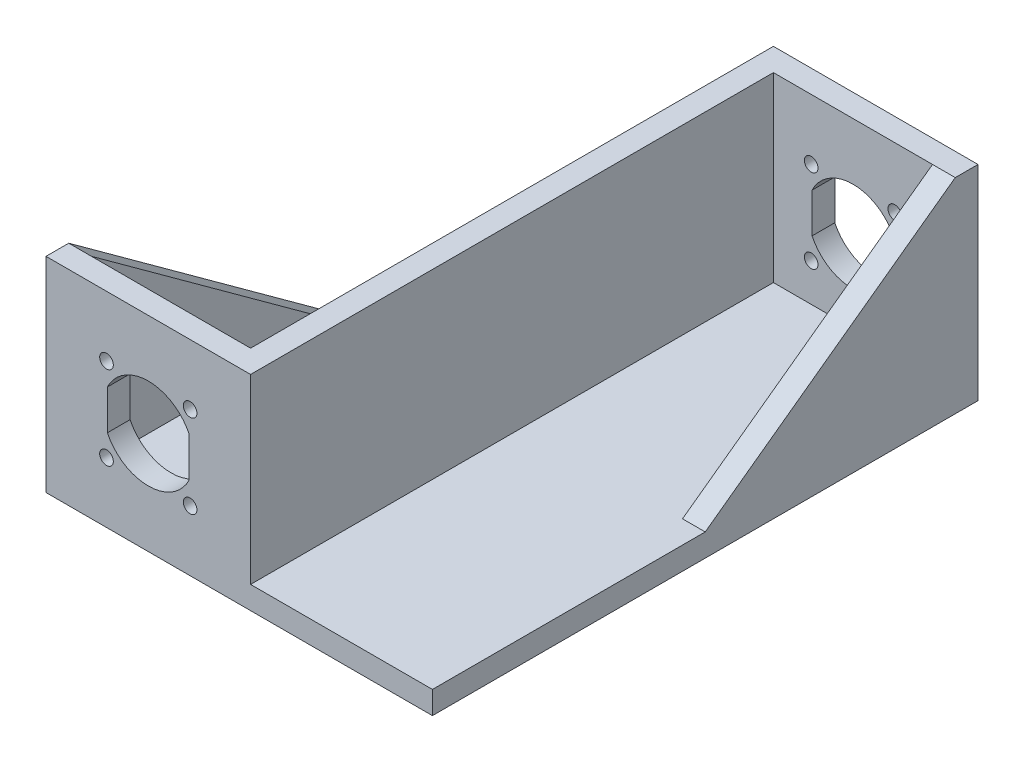
SolidWorks part; units mm, degrees
ref_plane "Plan de face" through (0, 0, 0) normal (0, 0, 1) x (1, 0, 0)
ref_plane "Plan de dessus" through (0, 0, 0) normal (0, 1, 0) x (1, 0, 0)
ref_plane "Plan de droite" through (0, 0, 0) normal (1, 0, 0) x (0, 0, -1)
sketch "Esquisse1" plane through (0, 0, 0) normal (0, 0, 1) x (1, 0, 0)
  line L0 (45, 0) -> (0, 45) construction
  line L1 (0, 0) -> (45, 0)
  line L2 (0, 0) -> (0, 45)
  line L3 (0, 45) -> (45, 45)
  line L4 (45, 0) -> (45, 45)
  line L5 (0, 0) -> (45, 45) construction
  line L6 (22.5, 45) -> (22.5, 0) construction
  line L7 (13.5, 26.8589) -> (13.5, 18.1411)
  line L8 (45, 22.5) -> (0, 22.5) construction
  line L9 (31.5, 26.8589) -> (31.5, 18.1411)
  arc A0 (13.5, 18.1411) -> (31.5, 18.1411) centre (22.5, 22.5) ccw
  circle A1 centre (31.6924, 31.6924) radius 1.5
  circle A2 centre (31.6924, 13.3076) radius 1.5
  circle A3 centre (13.3076, 13.3076) radius 1.5
  circle A4 centre (13.3076, 31.6924) radius 1.5
  arc A5 (31.5, 26.8589) -> (13.5, 26.8589) centre (22.5, 22.5) ccw
  dimension "D3" = 20
  dimension "D5" = 3
  dimension "D1" = 45
  dimension "D2" = 45
  dimension "D4" = 13
  dimension "D6" = 9
extrude "Extrusion1" add sketch "Esquisse1" along normal blind 5
sketch "Esquisse2" plane through (0, 0, 5) normal (0, 0, 1) x (1, 0, 0)
  line L0 (45, 0) -> (45, 45) construction
  line L1 (0, 0) -> (45, 0)
  line L2 (0, 0) -> (0, 5)
  line L3 (0, 5) -> (45, 5)
  line L4 (45, 0) -> (45, 5)
  dimension "D1" = 5
extrude "Extrusion2" add sketch "Esquisse2" along normal blind 115
sketch "Esquisse3" plane through (45, 0, 0) normal (1, 0, 0) x (0, 0, -1)
  line L0 (-5, 5) -> (-5, 45)
  line L1 (-5, 45) -> (-60, 5)
  line L2 (-120, 5) -> (-5, 5) construction
  line L3 (-60, 5) -> (-5, 5)
  dimension "D1" = 55
extrude "Extrusion3" add sketch "Esquisse3" against normal blind 5
sketch "Esquisse4" plane through (0, 0, 0) normal (-1, 0, 0) x (0, 0, 1)
  line L0 (5, 5) -> (5, 45)
  line L1 (5, 45) -> (120, 45)
  line L2 (120, 45) -> (120, 5)
  line L3 (120, 5) -> (5, 5)
extrude "Extrusion4" add sketch "Esquisse4" against normal blind 5
sketch "Esquisse5" plane through (0, 0, 0) normal (-1, 0, 0) x (0, 0, 1)
  line L0 (120, 45) -> (120, 0) construction
  line L1 (0, 0) -> (120, 0)
  line L2 (0, 0) -> (0, 5)
  line L3 (0, 5) -> (120, 5)
  line L4 (120, 0) -> (120, 5)
  dimension "D1" = 5
extrude "Extrusion5" add sketch "Esquisse5" along normal blind 40
sketch "Esquisse6" plane through (0, 0, 120) normal (0, 0, 1) x (1, 0, 0)
  line L0 (0, 5) -> (0, 45)
  line L1 (0, 45) -> (-40, 45)
  line L2 (-40, 45) -> (-40, 5)
  line L3 (-40, 5) -> (0, 5)
extrude "Extrusion6" add sketch "Esquisse6" against normal blind 5
sketch "Esquisse7" plane through (-40, 0, 0) normal (-1, 0, 0) x (0, 0, 1)
  line L0 (115, 5) -> (115, 45)
  line L1 (115, 45) -> (60, 5)
  line L2 (115, 5) -> (0, 5) construction
  line L3 (60, 5) -> (115, 5)
  dimension "D1" = 55
extrude "Extrusion7" add sketch "Esquisse7" against normal blind 5
sketch "Esquisse8" plane through (0, 0, 120) normal (0, 0, 1) x (1, 0, 0)
  line L0 (5, 5) -> (5, 0) construction
  line L1 (-40, 0) -> (45, 0) construction
  line L2 (5, 0) -> (-40, 45) construction
  line L3 (-40, 22.5) -> (5, 22.5) construction
  line L5 (-26.5, 18.1411) -> (-26.5, 26.8589)
  line L6 (-40, 0) -> (-40, 45) construction
  line L7 (5, 5) -> (5, 45) construction
  line L8 (5, 45) -> (-40, 0) construction
  line L9 (-8.5, 18.1411) -> (-8.5, 26.8589)
  line L10 (5, 45) -> (-40, 45) construction
  line L11 (-17.5, 45) -> (-17.5, 0) construction
  arc A0 (-26.5, 18.1411) -> (-8.5, 18.1411) centre (-17.5, 22.5) ccw
  circle A1 centre (-26.6924, 31.6924) radius 1.5
  circle A2 centre (-26.6924, 13.3076) radius 1.5
  circle A3 centre (-8.3076, 13.3076) radius 1.5
  circle A4 centre (-8.3076, 31.6924) radius 1.5
  arc A5 (-8.5, 26.8589) -> (-26.5, 26.8589) centre (-17.5, 22.5) ccw
  dimension "D1" = 20
  dimension "D2" = 3
  dimension "D3" = 13
  dimension "D4" = 9
extrude "Enlèv. mat.-Extru.1" cut sketch "Esquisse8" against normal up to next
